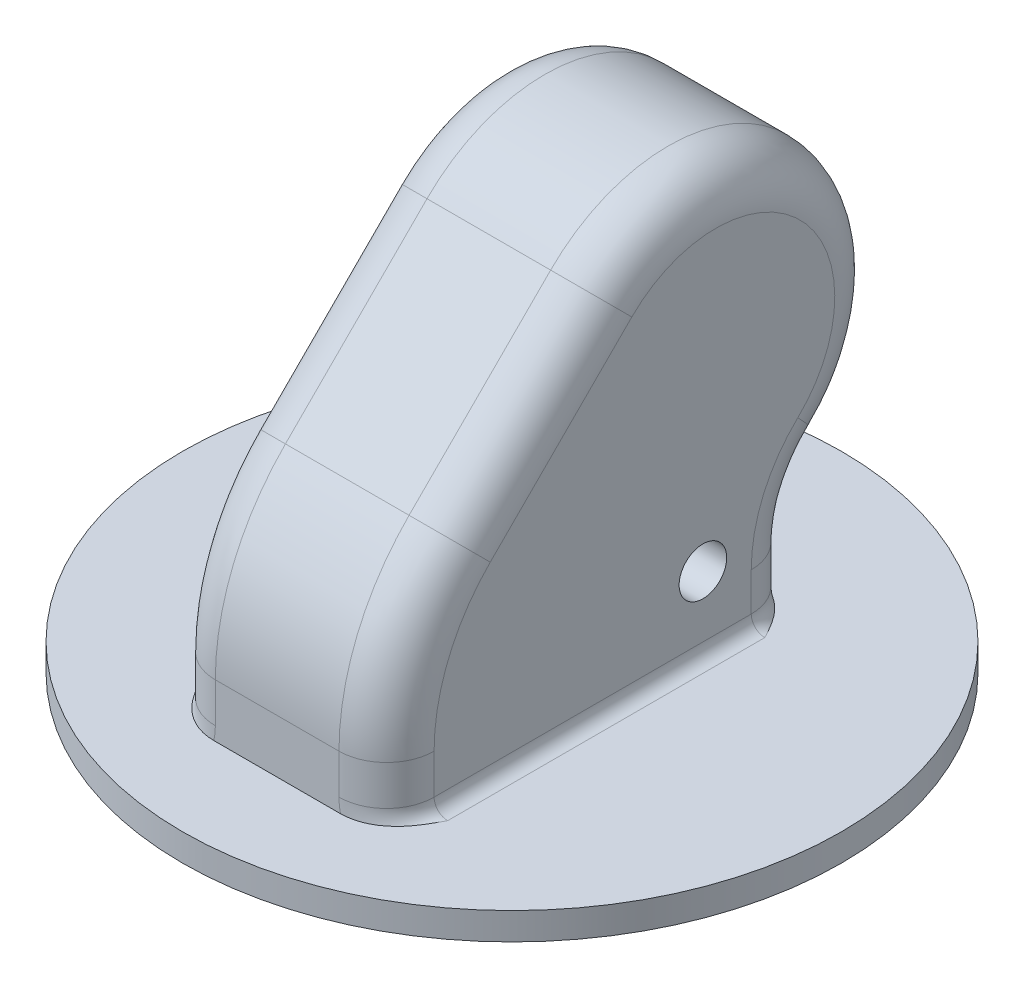
SolidWorks part; units mm, degrees
ref_plane "Front Plane" through (0, 0, 0) normal (0, 0, 1) x (1, 0, 0)
ref_plane "Top Plane" through (0, 0, 0) normal (0, 1, 0) x (1, 0, 0)
ref_plane "Right Plane" through (0, 0, 0) normal (1, 0, 0) x (0, 0, -1)
sketch "Sketch1" plane through (0, 0, 0) normal (0, 1, 0) x (1, 0, 0)
  line L1 (0, 7.25) -> (0, -7.25) construction
  circle A0 centre (0, 0) radius 48.5
  circle A3 centre (0, 7.25) radius 1.5
  circle A4 centre (0, -7.25) radius 1.5
  dimension "D1" = 97
  dimension "D6" = 3
  dimension "D5" = 14.5
extrude "Boss-Extrude1" add sketch "Sketch1" along normal blind 4
sketch "Sketch2" plane through (0, 0, 0) normal (0, -1, 0) x (1, 0, 0)
  circle A0 centre (0, 0) radius 3.75
  dimension "D1" = 7.5
extrude "Cut-Extrude1" cut sketch "Sketch2" against normal blind 1.5
ref_plane "Plane1" through (-16.1, 0, 0) normal (1, 0, 0) x (0, 0, -1)
sketch "Sketch3" plane through (-16.1, 0, 0) normal (1, 0, 0) x (0, 0, -1)
  line L0 (-34.5671, 4) -> (-34.5671, 11.86)
  line L4 (48.5, 4) -> (-48.5, 4) construction
  line L5 (-24.2495, 36.7687) -> (-3.4141, 57.6041)
  line L6 (26.1129, 11.64) -> (26.1129, 4)
  line L7 (-34.5671, 4) -> (26.1129, 4)
  arc A0 (-34.5671, 11.86) -> (-24.2495, 36.7687) centre (0.6592, 11.86) cw
  arc A1 (-3.4141, 57.6041) -> (30.7827, 22.5159) centre (13.91, 40.28) cw
  arc A2 (30.7827, 22.5159) -> (26.1129, 11.64) centre (41.1129, 11.64) ccw
  dimension "D7" = 24.5
  dimension "D8" = 15
  dimension "D9" = 35.2262
  dimension "D1" = 7.86
  dimension "D2" = 7.64
  dimension "D3" = 40.28
  dimension "D4" = 45
  dimension "D5" = 60.68
  dimension "D6" = 13.91
extrude "Boss-Extrude2" add sketch "Sketch3" along normal blind 16.1
ref_plane "Plane2" through (-14.1, 0, 0) normal (1, 0, 0) x (0, 0, -1)
sketch "Sketch4" plane through (-14.1, 0, 0) normal (1, 0, 0) x (0, 0, -1)
  line L0 (13.7417, 54.2538) -> (27.8838, 40.1117)
  line L5 (13.7417, 54.2538) -> (-15.9568, 24.5554)
  line L6 (27.8838, 40.1117) -> (-1.8146, 10.4132)
  line L7 (-15.9568, 24.5554) -> (-1.8146, 10.4132)
  line L8 (13.7417, 54.2538) -> (13.91, 40.28) construction
  line L9 (13.91, 40.28) -> (27.8838, 40.1117) construction
  line L10 (-34.5671, 4) -> (-8.75, 4) construction
  line L11 (13.91, 40.28) -> (20.8128, 47.1828) construction
  line L12 (20.7067, 54.1478) -> (21.4668, 53.3876) construction
  line L13 (-1.1075, 39.4046) -> (13.0346, 25.2625) construction
  point P0 (0, 29.3545)
  dimension "D1" = 91.38
  dimension "D2" = 45
  dimension "D3" = 20
  dimension "D4" = 42
  dimension "D8" = 5
  dimension "D9" = 4.85
extrude "Cut-Extrude3" cut sketch "Sketch4" along normal up to surface (14.1 mm away) up to face at (0, 16.6559, -0.0352)
sketch "Sketch5" plane through (0, 0, 0) normal (1, 0, 0) x (0, 0, -1)
  line L0 (-5.5354, 59.7254) -> (-26.3708, 38.89)
  line L1 (-37.5671, 11.86) -> (-37.5671, 1)
  line L2 (-37.5671, 1) -> (29.1129, 1)
  line L3 (29.1129, 1) -> (29.1129, 11.64)
  line L4 (-34.5671, 4) -> (-8.75, 4)
  line L5 (26.1129, 4) -> (26.1129, 11.64)
  line L6 (-3.4141, 57.6041) -> (-24.2495, 36.7687)
  line L7 (-34.5671, 11.86) -> (-34.5671, 4)
  line L8 (-28.5671, 4) -> (23.1129, 4)
  line L14 (-1.2928, 55.4828) -> (-22.1282, 34.6474) construction
  line L16 (-31.5671, 7) -> (23.1129, 7) construction
  line L17 (-31.5671, 11.86) -> (-31.5671, 7) construction
  line L18 (23.1129, 7) -> (23.1129, 11.64) construction
  line L19 (-34.5671, 4) -> (-8.75, 4) construction
  line L20 (23.1129, 11.64) -> (23.1129, 4)
  line L21 (-34.5671, 4) -> (26.1129, 4) construction
  line L22 (26.1129, 4) -> (26.1129, 11.64) construction
  line L23 (48.5, 4) -> (-48.5, 4) construction
  line L24 (-28.5671, 4) -> (23.1129, 4)
  line L25 (23.1129, 11.64) -> (23.1129, 4)
  line L26 (-34.5671, 11.86) -> (-34.5671, 4) construction
  line L27 (-3.4141, 57.6041) -> (-24.2495, 36.7687) construction
  line L36 (-8.75, 4) -> (-5.75, 4)
  line L37 (-8.75, 4) -> (-5.75, 4)
  line L38 (-5.75, 4) -> (5.75, 4)
  line L39 (-5.75, 4) -> (5.75, 4)
  line L40 (5.75, 4) -> (8.75, 4)
  line L41 (5.75, 4) -> (8.75, 4)
  line L42 (8.75, 4) -> (26.1129, 4)
  line L43 (8.75, 4) -> (26.1129, 4)
  arc A0 (-26.3708, 38.89) -> (-37.5671, 11.86) centre (0.6592, 11.86) ccw
  arc A1 (32.8488, 20.3408) -> (29.1129, 11.64) centre (41.1129, 11.64) ccw
  arc A2 (32.8488, 20.3408) -> (-5.5354, 59.7254) centre (13.91, 40.28) ccw
  arc A3 (30.7827, 22.5159) -> (26.1129, 11.64) centre (41.1129, 11.64) ccw
  arc A4 (30.7827, 22.5159) -> (-3.4141, 57.6041) centre (13.91, 40.28) ccw
  arc A5 (-24.2495, 36.7687) -> (-34.5671, 11.86) centre (0.6592, 11.86) ccw
  arc A9 (28.7167, 24.6911) -> (23.1129, 11.64) centre (41.1129, 11.64) ccw
  arc A10 (28.7167, 24.6911) -> (-1.2928, 55.4828) centre (13.91, 40.28) ccw
  arc A12 (-1.2928, 55.4828) -> (-28.5671, 4) centre (68.8139, -14.6239) ccw
  arc A13 (30.7827, 22.5159) -> (-3.4141, 57.6041) centre (13.91, 40.28) ccw construction
  arc A14 (-22.1282, 34.6474) -> (-31.5671, 11.86) centre (0.6592, 11.86) ccw construction
  arc A15 (-24.2495, 36.7687) -> (-34.5671, 11.86) centre (0.6592, 11.86) ccw construction
  arc A16 (30.7827, 22.5159) -> (26.1129, 11.64) centre (41.1129, 11.64) ccw construction
  line M28 (-34.5671, 4) -> (-8.75, 4)
  line M35 (-1.8146, 10.4132) -> (-15.9568, 24.5554)
  line M36 (-15.9568, 24.5554) -> (13.7417, 54.2538)
  line M37 (13.7417, 54.2538) -> (27.8838, 40.1117)
  line M38 (27.8838, 40.1117) -> (-1.8146, 10.4132)
  line M63 (-8.75, 4) -> (-5.75, 4)
  line M64 (-5.75, 4) -> (5.75, 4)
  line M65 (5.75, 4) -> (8.75, 4)
  line M66 (8.75, 4) -> (26.1129, 4)
  dimension "D1" = 0
  dimension "D2" = 3
  dimension "D3" = 3
fillet "Fillet3" radius 2 1 edges at (-16.1, 4, 4.2271)
extrude "Cut-Extrude4" cut sketch "Sketch5" against normal blind 10.1 contours A10 A12 L20 A9 M28 M63 M64 M65 M66 M38 M35 M36 M37 region at (0, 31.3864, 18.0351)
mirror "Mirror6" about plane through (0, 11.64, -41.1129) normal (1, 0, 0) of bodies 109
sketch "Sketch6" plane through (-16.1, 0, 0) normal (-1, 0, 0) x (0, 0, 1)
  line L0 (-27.8838, 40.1117) -> (1.8146, 10.4132) construction
  line L1 (15.9568, 24.5554) -> (1.8146, 10.4132) construction
  line L2 (-13.7417, 54.2538) -> (15.9568, 24.5554) construction
  line L3 (-13.7417, 54.2538) -> (-27.8838, 40.1117) construction
  line L4 (-27.8838, 40.1117) -> (1.8146, 10.4132)
  line L5 (15.9568, 24.5554) -> (1.8146, 10.4132)
  line L6 (-13.7417, 54.2538) -> (15.9568, 24.5554)
  line L7 (-13.7417, 54.2538) -> (-27.8838, 40.1117)
extrude "Cut-Extrude5" cut sketch "Sketch6" against normal blind 5
sketch "Sketch7" plane through (-16.1, 0, 0) normal (-1, 0, 0) x (0, 0, 1)
  line L0 (-20.7067, 54.1478) -> (-27.7778, 47.0767) construction
  line L2 (7.5069, 11.7921) -> (14.5779, 18.8631) construction
  line L3 (-24.2422, 50.6122) -> (11.0424, 15.3276) construction
  line L10 (-26.1129, 6) -> (-26.1129, 11.64) construction
  line L11 (-26.1129, 6) -> (34.5671, 6) construction
  circle A0 centre (-20.7067, 54.1478) radius 2.1
  circle A1 centre (-27.7778, 47.0767) radius 2.1
  circle A2 centre (14.5779, 18.8631) radius 2.1
  circle A3 centre (7.5069, 11.7921) radius 2.1
  dimension "D4" = 4.2
  dimension "D1" = 5.4062
  dimension "D2" = 33.6198
  dimension "D3" = 10
  dimension "D5" = 49.9
  dimension "D6" = 40.6909
  dimension "D7" = 5.7921
extrude "Cut-Extrude6" cut sketch "Sketch7" against normal up to next
fillet "Fillet4" radius 7 16 edges at (16.6858, 4.5858, -26.1129) (16.1, 8.82, -26.1129) (16.1, 17.558, -27.3297) (16.6858, 4.5858, 34.5671) (16.1, 8.93, 34.5671) (16.1, 25.3405, 31.8856) (16.1, 47.1864, 13.8318) (-16.6858, 4.5858, -26.1129) (-16.1, 8.82, -26.1129) (-16.1, 17.558, -27.3297) (-16.6858, 4.5858, 34.5671) (-16.1, 8.93, 34.5671) (-16.1, 25.3405, 31.8856) (-16.1, 47.1864, 13.8318) (16.1, 57.3798, -31.4555) (-16.1, 57.3798, -31.4555)
sketch "Sketch8" plane through (0, 0, 0) normal (0, -1, 0) x (1, 0, 0)
  line L1 (3.5106, 26.056) -> (-3.4894, 26.0683)
  line L2 (-3.4894, 26.0683) -> (-7, 20.0123)
  line L3 (-7, 20.0123) -> (-3.5106, 13.944)
  line L4 (-3.5106, 13.944) -> (3.4894, 13.9317)
  line L5 (3.4894, 13.9317) -> (7, 19.9877)
  line L6 (7, 19.9877) -> (3.5106, 26.056)
  circle A0 centre (0, 20) radius 6.0622 construction
  dimension "D1" = 7
  dimension "D2" = 20
extrude "Cut-Extrude7" cut sketch "Sketch8" against normal up to next
sketch "Sketch10" plane through (16.1, 0, 0) normal (1, 0, 0) x (0, 0, -1)
  circle A0 centre (12, 15) radius 3.5
  dimension "D1" = 7
  dimension "D2" = 12
  dimension "D3" = 15
extrude "Cut-Extrude9" cut sketch "Sketch10" against normal up to next
